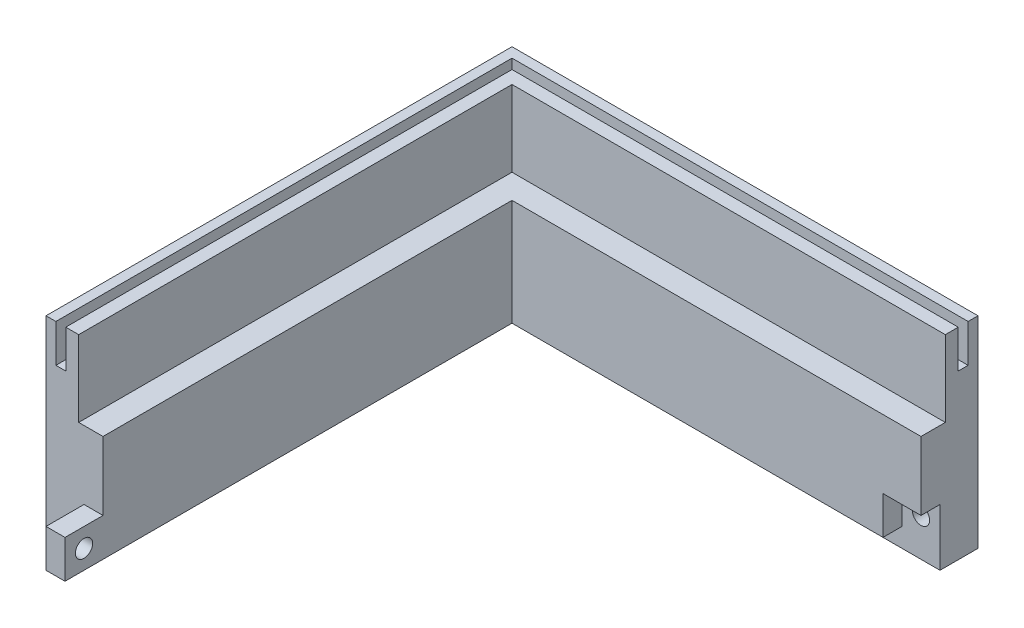
SolidWorks part; units mm, degrees
ref_plane "Front Plane" through (0, 0, 0) normal (0, 0, 1) x (1, 0, 0)
ref_plane "Top Plane" through (0, 0, 0) normal (0, 1, 0) x (1, 0, 0)
ref_plane "Right Plane" through (0, 0, 0) normal (1, 0, 0) x (0, 0, -1)
sketch "Sketch1" plane through (0, 0, 0) normal (0, 1, 0) x (1, 0, 0)
  line L7 (-60.6056, 37.6635) -> (95.0964, 37.6635)
  line L12 (95.0964, 37.6635) -> (95.0964, 18.6135)
  line L13 (95.0964, 18.6135) -> (-41.5556, 18.6135)
  line L14 (-41.5556, 18.6135) -> (-41.5556, -118.0385)
  line L15 (-41.5556, -118.0385) -> (-60.6056, -118.0385)
  line L16 (-60.6056, -118.0385) -> (-60.6056, 37.6635)
  line L17 (-57.3036, -118.0385) -> (-57.3036, 34.3615)
  line L18 (-57.3036, 34.3615) -> (95.0964, 34.3615)
  line L19 (-54.0016, -118.0385) -> (-54.0016, 31.0595)
  line L20 (-54.0016, 31.0595) -> (95.0964, 31.0595)
  line L21 (95.0964, 27.7575) -> (-50.6996, 27.7575)
  line L22 (-50.6996, 27.7575) -> (-50.6996, -118.0385)
  dimension "D1" = 155.702
  dimension "D2" = 19.05
  dimension "D3" = 3.302
  dimension "D4" = 3.302
  dimension "D5" = 3.302
extrude "Boss-Extrude5" add sketch "Sketch1" along normal blind 67.31 contours L14 L15 L16 L7 L12 L13
sketch "Sketch8" plane through (0, 67.31, 0) normal (0, 1, 0) x (1, 0, 0)
  line L0 (-57.3036, -118.0385) -> (-57.3036, 34.3615)
  line L1 (-57.3036, -118.0385) -> (-54.0016, -118.0385)
  line L2 (95.0964, 34.3615) -> (95.0964, 31.0595)
  line L3 (-41.5556, -118.0385) -> (-60.6056, -118.0385) construction
  line L4 (-57.3036, 34.3615) -> (95.0964, 34.3615)
  line L5 (95.0964, 37.6635) -> (95.0964, 18.6135) construction
  line L6 (-60.6056, -118.0385) -> (-60.6056, 37.6635) construction
  line L7 (-54.0016, -118.0385) -> (-54.0016, 31.0595)
  line L8 (-54.0016, 31.0595) -> (95.0964, 31.0595)
  dimension "D1" = 3.302
  dimension "D2" = 3.302
extrude "Cut-Extrude2" cut sketch "Sketch8" against normal blind 12.6933
sketch "Sketch9" plane through (0, 67.31, 0) normal (0, 1, 0) x (1, 0, 0)
  line L0 (-49.6836, -118.0385) -> (-49.6836, 26.7415)
  line L1 (-41.5556, -118.0385) -> (-54.0016, -118.0385) construction
  line L2 (-49.6836, 26.7415) -> (95.0964, 26.7415)
  line L3 (95.0964, 31.0595) -> (95.0964, 18.6135) construction
  line L4 (95.0964, 26.7415) -> (95.0964, 18.6135)
  line L5 (95.0964, 18.6135) -> (-41.5556, 18.6135)
  line L6 (-41.5556, 18.6135) -> (-41.5556, -118.0385)
  line L7 (-41.5556, -118.0385) -> (-49.6836, -118.0385)
  dimension "D1" = 4.318
extrude "Cut-Extrude3" cut sketch "Sketch9" against normal blind 25.4
sketch "Sketch15" plane through (0, 0, 0) normal (0, -1, 0) x (1, 0, 0)
  line L0 (-41.5556, 118.0385) -> (-47.9056, 118.0385)
  line L1 (-41.5556, 118.0385) -> (-60.6056, 118.0385) construction
  line L2 (-47.9056, 118.0385) -> (-47.9056, -24.9635)
  line L3 (-47.9056, -24.9635) -> (95.0964, -24.9635)
  line L4 (95.0964, -37.6635) -> (95.0964, -18.6135) construction
  line L5 (95.0964, -24.9635) -> (95.0964, -18.6135)
  line L6 (95.0964, -18.6135) -> (-41.5556, -18.6135)
  line L7 (-41.5556, -18.6135) -> (-41.5556, 118.0385)
  dimension "D1" = 6.35
extrude "Cut-Extrude5" cut sketch "Sketch15" against normal blind 6.35
sketch "Sketch16" plane through (0, 0, 118.0385) normal (0, 0, 1) x (1, 0, 0)
  line L0 (-41.5556, 41.91) -> (-41.5556, 6.35) construction
  line L1 (-47.9056, 6.35) -> (-41.5556, 6.35)
  line L2 (-47.9056, 6.35) -> (-47.9056, 19.05)
  line L3 (-47.9056, 19.05) -> (-41.5556, 19.05)
  line L4 (-41.5556, 6.35) -> (-41.5556, 19.05)
  dimension "D1" = 12.7
extrude "Boss-Extrude6" add sketch "Sketch16" along normal blind 12.7
sketch "Sketch17" plane through (95.0964, 0, 0) normal (1, 0, 0) x (0, 0, -1)
  line L0 (18.6135, 41.91) -> (18.6135, 6.35) construction
  line L1 (24.9635, 6.35) -> (18.6135, 6.35)
  line L2 (24.9635, 6.35) -> (24.9635, 19.05)
  line L3 (24.9635, 19.05) -> (18.6135, 19.05)
  line L4 (18.6135, 6.35) -> (18.6135, 19.05)
  dimension "D1" = 12.7
extrude "Cut-Extrude6" cut sketch "Sketch17" against normal blind 12.7
sketch "Sketch18" plane through (-41.5556, 0, 0) normal (1, 0, 0) x (0, 0, -1)
  line L0 (-130.7385, 12.7) -> (-118.0385, 12.7)
  line L1 (-118.0385, 19.05) -> (-130.7385, 19.05)
  line L2 (-118.0385, 19.05) -> (-118.0385, 6.35)
  line L3 (-118.0385, 6.35) -> (-130.7385, 6.35)
  line L4 (-130.7385, 19.05) -> (-130.7385, 6.35)
  line L5 (-124.3885, 19.05) -> (-124.3885, 6.35)
  circle A0 centre (-124.3885, 12.7) radius 2.8829
  dimension "D1" = 5.7658
extrude "Cut-Extrude7" cut sketch "Sketch18" against normal blind 12.7 contours A0
sketch "Sketch19" plane through (0, 0, -24.9635) normal (0, 0, 1) x (1, 0, 0)
  line L0 (95.0964, 12.7) -> (82.3964, 12.7)
  line L1 (82.3964, 6.35) -> (95.0964, 6.35)
  line L2 (82.3964, 6.35) -> (82.3964, 19.05)
  line L3 (82.3964, 19.05) -> (95.0964, 19.05)
  line L4 (95.0964, 6.35) -> (95.0964, 19.05)
  circle A0 centre (88.7464, 12.7) radius 2.8829
  dimension "D1" = 5.7658
extrude "Cut-Extrude8" cut sketch "Sketch19" against normal blind 4.826 contours A0
sketch "Sketch21" plane through (0, 6.35, 0) normal (0, -1, 0) x (1, 0, 0)
  line L0 (-41.5556, -18.6135) -> (-47.9056, -24.9635)
  circle A0 centre (-44.7306, -21.7885) radius 2.8829
  dimension "D1" = 5.7658
extrude "Cut-Extrude9" cut sketch "Sketch21" against normal blind 4.826 contours A0
